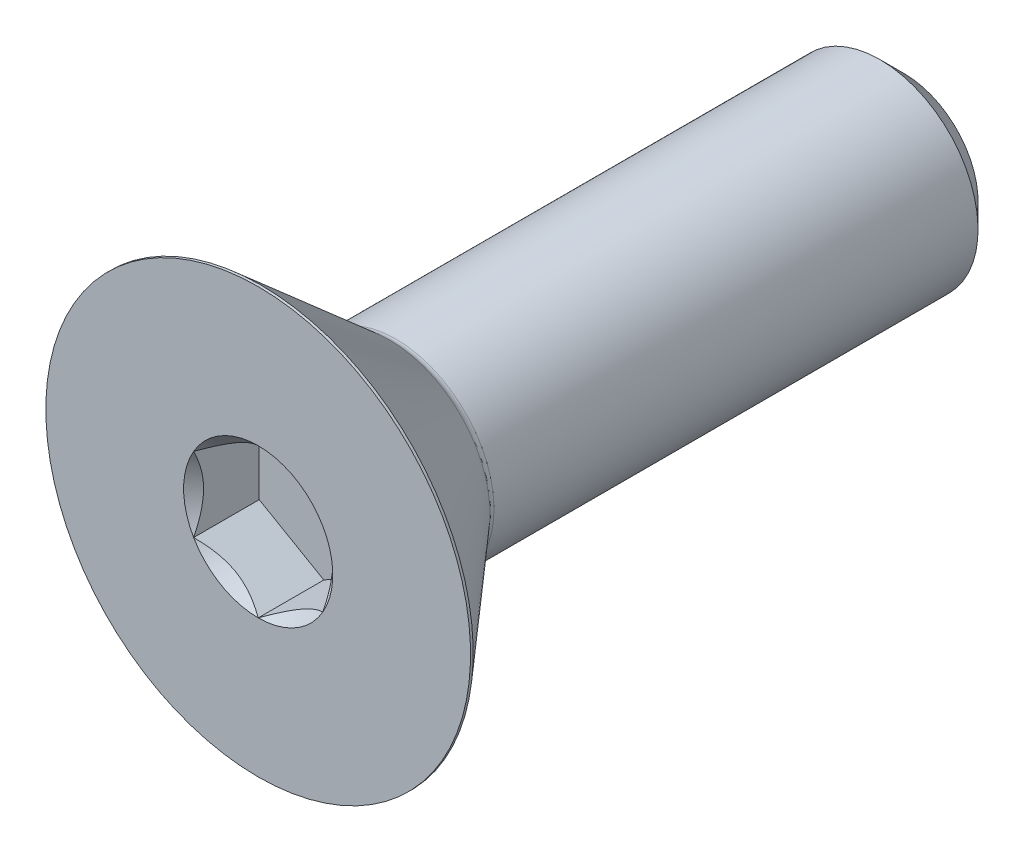
SolidWorks part; units mm, degrees
ref_plane "Front Plane" through (0, 0, 0) normal (0, 0, 1) x (1, 0, 0)
ref_plane "Top Plane" through (0, 0, 0) normal (0, 1, 0) x (1, 0, 0)
ref_plane "Right Plane" through (0, 0, 0) normal (1, 0, 0) x (0, 0, -1)
sketch "Sketch1" plane through (0, 0, 0) normal (1, 0, 0) x (0, 0, -1)
  line L0 (-7.9375, 0) -> (7.9375, 0) construction
  line L1 (-7.9375, 0) -> (-7.9375, 5.2197)
  line L2 (-7.9375, 5.2197) -> (-7.873, 5.2197)
  line L3 (-7.873, 5.2197) -> (-4.7117, 2.4716)
  line L4 (-7.873, -5.2197) -> (-4.7117, -2.4716)
  line L5 (7.9375, 0) -> (7.9375, 2.413)
  line L6 (7.9375, 2.413) -> (-4.7117, 2.413)
  line L7 (7.3422, 2.413) -> (7.9375, 1.8177)
  line L8 (7.8879, 2.4989) -> (8.2848, 1.8115) construction
  line L9 (8.2848, 1.8115) -> (8.6816, 2.4989) construction
  line L10 (8.6816, 2.4989) -> (7.8879, 2.4989) construction
  line L11 (7.9127, 2.456) -> (8.6568, 2.456)
  line L12 (8.6568, 2.456) -> (8.3344, 1.8974)
  line L13 (8.3344, 1.8974) -> (8.2352, 1.8974)
  line L14 (8.2352, 1.8974) -> (7.9127, 2.456)
  line L15 (8.2848, 1.8974) -> (8.2848, 1.8115) construction
  line L16 (7.9375, 2.413) -> (8.632, 2.413) construction
  line L17 (8.2848, 2.4989) -> (8.2848, 2.413) construction
  line L18 (7.9375, -2.413) -> (-4.7117, -2.413)
  arc A0 (-4.7117, 2.4716) -> (-4.5549, 2.413) centre (-4.5549, 2.6521) ccw
  point P2 (0, 0)
  point P23 (-6.3246, 0)
  point P27 (8.2848, 2.456)
  point P30 (6.7469, -2.413)
  point P31 (-4.7117, 5.2197)
  point P34 (-7.873, -5.2197)
  dimension "Length" = 15.875
  dimension "Head Height" = 3.2258
  dimension "Head Diameter" = 10.4394
  dimension "Countersink Angle" = 82
  dimension "Screw Size Decimal Equivalent" = 4.826
  dimension "Pitch" = 0.7937
  dimension "D4" = 0.0992
  dimension "D3" = 45
  dimension "D5" = 0.5953
  dimension "D6" = 1.6129
  dimension "D1" = 1.1906
  dimension "D7" = 0.0645
sketch "Sketch8" plane through (0, 0, 0) normal (0, 0, 1) x (1, 0, 0)
  line L1 (0, 1.8331) -> (-1.5875, 0.9165)
  line L2 (-1.5875, 0.9165) -> (-1.5875, -0.9165)
  line L3 (-1.5875, -0.9165) -> (0, -1.8331)
  line L4 (0, -1.8331) -> (1.5875, -0.9165)
  line L5 (1.5875, -0.9165) -> (1.5875, 0.9165)
  line L6 (1.5875, 0.9165) -> (0, 1.8331)
  circle A0 centre (0, 0) radius 1.5875 construction
  dimension "Drive Size" = 3.175
sketch "Sketch2" plane through (0, 0, 0) normal (1, 0, 0) x (0, 0, -1)
  line L0 (-7.873, 5.2197) -> (-4.7117, 2.4716) construction
  line L1 (-7.9375, 0) -> (-7.9375, 5.2197) construction
  line L2 (-7.873, 5.2197) -> (-4.7117, 2.4716)
  line L3 (-7.9375, 0) -> (-7.9375, 5.2197)
  line L4 (-7.9375, 5.2197) -> (-7.873, 5.2197) construction
  line L5 (-7.9375, 5.2197) -> (-7.873, 5.2197)
  line L6 (-4.5549, 2.413) -> (7.3422, 2.413)
  line L7 (7.3422, 2.413) -> (7.9375, 1.8177)
  line L8 (7.9375, 1.8177) -> (7.9375, 0)
  line L9 (7.9375, 0) -> (-7.9375, 0)
  arc A0 (-4.7117, 2.4716) -> (-4.5549, 2.413) centre (-4.5549, 2.6521) ccw construction
  arc A1 (-4.7117, 2.4716) -> (-4.5549, 2.413) centre (-4.5549, 2.6521) ccw
revolve "Revolve1" add sketch "Sketch2" angle 360 about L9
sketch "Sketch9" plane through (0, 0, 7.9375) normal (0, 0, 1) x (1, 0, 0)
  line L0 (1.5875, -0.9165) -> (1.5875, 0.9165) construction
  line L1 (0, -1.8331) -> (1.5875, -0.9165) construction
  line L2 (-1.5875, -0.9165) -> (0, -1.8331) construction
  line L3 (-1.5875, 0.9165) -> (-1.5875, -0.9165) construction
  line L4 (0, 1.8331) -> (-1.5875, 0.9165) construction
  line L5 (1.5875, 0.9165) -> (0, 1.8331) construction
  line L6 (1.5875, -0.9165) -> (1.5875, 0.9165)
  line L7 (0, -1.8331) -> (1.5875, -0.9165)
  line L8 (-1.5875, -0.9165) -> (0, -1.8331)
  line L9 (-1.5875, 0.9165) -> (-1.5875, -0.9165)
  line L10 (0, 1.8331) -> (-1.5875, 0.9165)
  line L11 (1.5875, 0.9165) -> (0, 1.8331)
sketch "Sketch10" plane through (0, 0, 7.9375) normal (0, 0, 1) x (1, 0, 0)
  circle A0 centre (0, 0) radius 1.8331
extrude "Cut-Extrude2" cut sketch "Sketch10" against normal up to vertex (1.6129 mm away) draft 45 up to point (0, 0, 6.3246)
extrude "Cut-Extrude1" cut sketch "Sketch9" against normal up to vertex (1.6129 mm away) up to point (0, 0, 6.3246)
ref_plane "Plane1" [suppressed] through (0, 0, 4.5549) normal (0, 0, 1) x (1, 0, 0)
split "Split1" [suppressed] bodies to split 111
sketch "Sketch3" [suppressed] plane through (0, 0, -7.9375) normal (0, 0, -1) x (-1, 0, 0)
  circle A0 centre (0, 0) radius 2.413 construction
  circle A1 centre (0, 0) radius 2.413
curve "Helix/Spiral1" [suppressed] pitch 0.7937 height 15.875 turns 20
sketch "Sketch4" [suppressed] plane through (0, 0, 0) normal (1, 0, 0) x (0, 0, -1)
  line L0 (7.9127, 2.456) -> (8.6568, 2.456) construction
  line L1 (8.2352, 1.8974) -> (7.9127, 2.456) construction
  line L2 (8.3344, 1.8974) -> (8.2352, 1.8974) construction
  line L3 (8.6568, 2.456) -> (8.3344, 1.8974) construction
  line L4 (7.9127, 2.456) -> (8.6568, 2.456)
  line L5 (8.2352, 1.8974) -> (7.9127, 2.456)
  line L6 (8.3344, 1.8974) -> (8.2352, 1.8974)
  line L7 (8.6568, 2.456) -> (8.3344, 1.8974)
sweep "Cut-Sweep1" [suppressed] cut profiles "Sketch4" path "Helix/Spiral1"
sketch "Sketch7" [suppressed] plane through (0, 0, 4.5549) normal (0, 0, 1) x (1, 0, 0)
  circle A0 centre (0, 0) radius 2.413
extrude "Boss-Extrude2" [suppressed] add sketch "Sketch7" against normal up to next draft 20
equation "\"D4@Sketch1\" = \"Pitch@Sketch1\" / 8"
equation "\"D5@Sketch1\"=\"Pitch@Sketch1\"*0.75"
equation "\"D4@Helix/Spiral1\"=\"Pitch@Sketch1\""
equation "\"D3@Helix/Spiral1\"=\"Length@Sketch1\""
equation "\"D6@Sketch1\"=\"Head Height@Sketch1\"/2"
equation "\"D1@Sketch1\"=\"Pitch@Sketch1\"*1.5"
equation "\"D7@Sketch1\"=\"Head Height@Sketch1\"*0.02"
